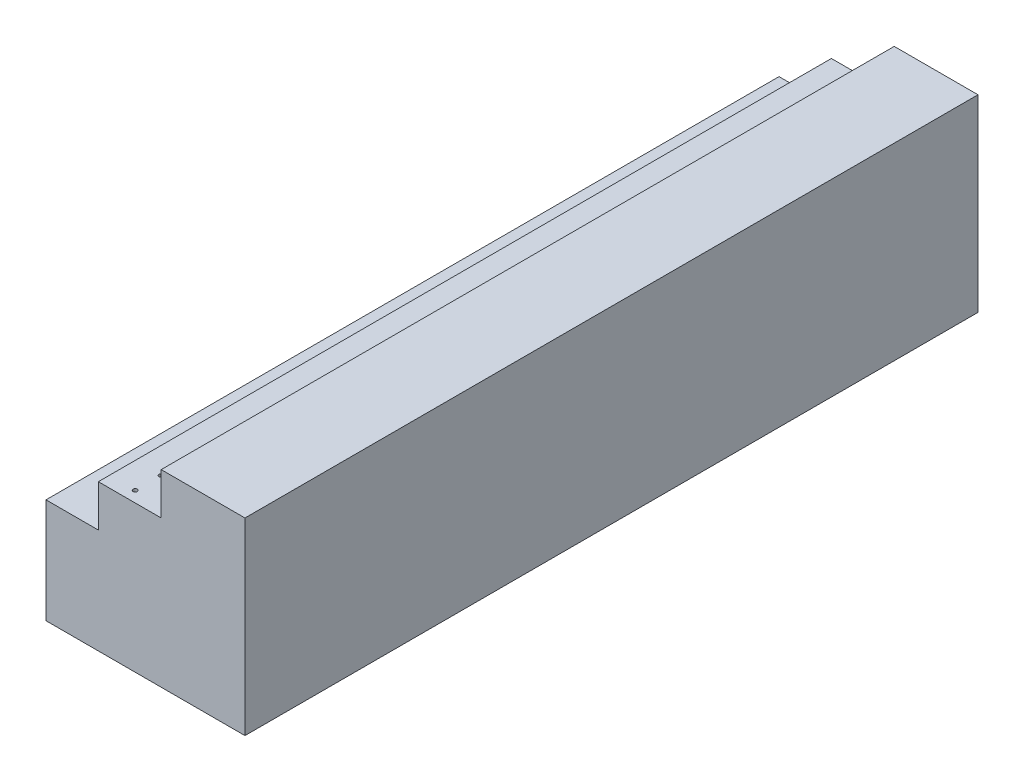
SolidWorks part; units mm, degrees
material "granite"
ref_plane "Front Plane" through (0, 0, 0) normal (0, 0, 1) x (1, 0, 0)
ref_plane "Top Plane" through (0, 0, 0) normal (0, 1, 0) x (1, 0, 0)
ref_plane "Right Plane" through (0, 0, 0) normal (1, 0, 0) x (0, 0, -1)
sketch "Эскиз1" plane through (0, 0, 0) normal (0, 1, 0) x (1, 0, 0)
  line L0 (1140, 3500) -> (1140, 0)
  line L1 (0, 0) -> (1200, 0)
  line L3 (0, 3500) -> (1200, 3500)
  line L4 (1200, 0) -> (1200, 3500)
  line L5 (250, 3500) -> (250, 0)
  line L6 (500, 3500) -> (500, 0)
  line L7 (800, 3500) -> (800, 0)
  dimension "D1" = 250
  dimension "D2" = 250
  dimension "D3" = 300
  dimension "D4" = 60
  dimension "D5" = 3500
  dimension "D6" = 1200
extrude "Бобышка-Вытянуть1" add sketch "Эскиз1" along normal blind 300 contours L5 L3 L1 region at (375, 0, -1750)
extrude "Бобышка-Вытянуть2" add sketch "Эскиз1<3>" along normal blind 500 contours L6 L3 L5 L1 region at (375, 0, -1750)
sketch "Эскиз1<3>" plane through (0, 0, 0) normal (0, 1, 0) x (1, 0, 0) same geometry as "Эскиз1"
extrude "Бобышка-Вытянуть3" add sketch "Эскиз1<4>" along normal blind 700 contours L7 L3 L6 L1 region at (650, 0, -1750)
sketch "Эскиз1<4>" plane through (0, 0, 0) normal (0, 1, 0) x (1, 0, 0) same geometry as "Эскиз1"
extrude "Бобышка-Вытянуть4" add sketch "Эскиз1<5>" along normal blind 900 contours L3 L7 L1 L0 region at (970, 0, -1750)
sketch "Эскиз1<5>" plane through (0, 0, 0) normal (0, 1, 0) x (1, 0, 0) same geometry as "Эскиз1"
extrude "Бобышка-Вытянуть5" add sketch "Эскиз1<6>" along normal blind 900 contours L1 L4 L3 L0 region at (1170, 0, -1750)
sketch "Эскиз1<6>" plane through (0, 0, 0) normal (0, 1, 0) x (1, 0, 0) same geometry as "Эскиз1"
sketch "Эскиз2" plane through (0, 700, 0) normal (0, 1, 0) x (1, 0, 0)
  circle A0 centre (625, 3357.1521) radius 10
  circle A1 centre (625, 3243.137) radius 10
  circle A2 centre (625, 3145.793) radius 10
  circle A3 centre (625, 3016.4639) radius 10
  circle A4 centre (625, 2886.8924) radius 10
  circle A6 centre (625, 2776.185) radius 10
  circle A7 centre (625, 2652.1125) radius 10
  circle A8 centre (625, 2528.6152) radius 10
  circle A9 centre (625, 2426.8665) radius 10
  circle A11 centre (625, 2323.054) radius 10
  circle A12 centre (625, 2236.3631) radius 12.336
extrude "Вырез-Вытянуть1" cut sketch "Эскиз2" against normal blind 230
sketch "Эскиз10" plane through (0, 700, 0) normal (0, 1, 0) x (1, 0, 0)
  circle A0 centre (632.852, 2116.6173) radius 10
  circle A1 centre (632.852, 2002.6022) radius 10
  circle A2 centre (632.852, 1905.2582) radius 10
  circle A3 centre (632.852, 1775.9291) radius 10
  circle A4 centre (632.852, 1646.3576) radius 10
  circle A6 centre (632.852, 1535.6502) radius 10
  circle A7 centre (632.852, 1411.5777) radius 10
  circle A8 centre (632.852, 1288.0804) radius 10
  circle A9 centre (632.852, 1186.3317) radius 10
  circle A11 centre (632.852, 1082.5192) radius 10
  circle A12 centre (632.852, 995.8283) radius 12.336
extrude "Вырез-Вытянуть8" cut sketch "Эскиз10" against normal blind 230
sketch "Эскиз16" plane through (0, 700, 0) normal (0, 1, 0) x (1, 0, 0)
  circle A0 centre (623.6728, 880.7229) radius 10
  circle A1 centre (623.6728, 766.7078) radius 10
  circle A2 centre (623.6728, 669.3637) radius 10
  circle A3 centre (623.6728, 540.0346) radius 10
  circle A4 centre (623.6728, 410.4632) radius 10
  circle A6 centre (623.6728, 299.7558) radius 10
  circle A7 centre (623.6728, 175.6833) radius 10
  circle A8 centre (623.6728, 52.186) radius 10
  circle A9 centre (623.6728, -49.5627) radius 10
  circle A11 centre (623.6728, -153.3752) radius 10
  circle A12 centre (623.6728, -240.0661) radius 12.336
extrude "Вырез-Вытянуть14" cut sketch "Эскиз16" against normal blind 230
